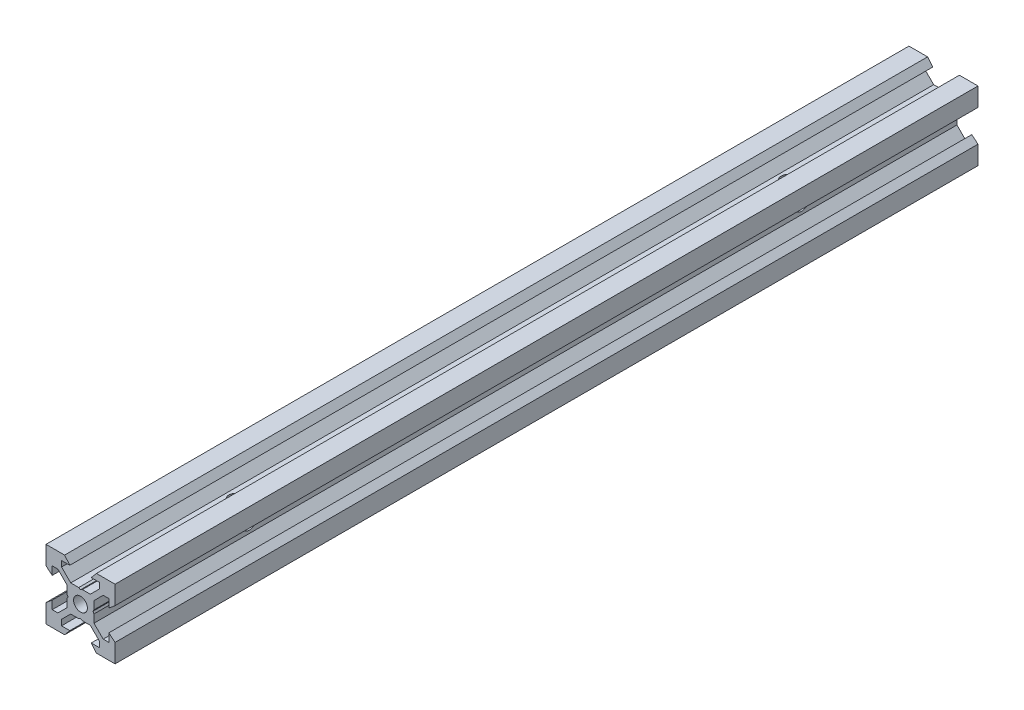
SolidWorks part; units mm, degrees
material "3.3535 (EN-AW 5754)"
ref_plane "Front Plane" through (0, 0, 0) normal (0, 0, 1) x (1, 0, 0)
ref_plane "Top Plane" through (0, 0, 0) normal (0, 1, 0) x (1, 0, 0)
ref_plane "Right Plane" through (0, 0, 0) normal (1, 0, 0) x (0, 0, -1)
sketch "Sketch1" plane through (0, 0, 0) normal (0, 0, 1) x (1, 0, 0)
  line L0 (10, 10) -> (4.6104, 10) construction
  line L1 (10, 10) -> (10, 4.6104) construction
  line L2 (10, -10) -> (10, -4.6104) construction
  line L3 (10, -10) -> (4.6104, -10) construction
  line L4 (10, 10) -> (10, 4.6104)
  line L5 (6.5607, 5.5) -> (8.2, 5.5)
  line L6 (5.5, 8.2) -> (5.5, 6.5607)
  line L7 (10, 10) -> (4.6104, 10)
  line L8 (10, 10) -> (10, 4.6104)
  line L9 (6.5607, 5.5) -> (3.9, 2.8393)
  line L10 (5.5, 6.5607) -> (2.8393, 3.9)
  line L11 (10, 4.6104) -> (8.2, 3.1)
  line L12 (4.6104, 10) -> (3.1, 8.2)
  line L13 (8.2, 3.1) -> (8.2, 5.5)
  line L14 (3.1, 8.2) -> (5.5, 8.2)
  line L15 (-6.5607, 5.5) -> (-8.2, 5.5)
  line L16 (6.5607, -5.5) -> (8.2, -5.5)
  line L17 (3.1, -8.2) -> (5.5, -8.2)
  line L18 (8.2, -3.1) -> (8.2, -5.5)
  line L19 (4.6104, -10) -> (3.1, -8.2)
  line L20 (10, -4.6104) -> (8.2, -3.1)
  line L21 (0.5196, -3.9) -> (0, -3.6)
  line L22 (0.5196, 3.9) -> (0, 3.6)
  line L23 (3.6, 0) -> (3.9, -0.5196)
  line L24 (3.9, 0.5196) -> (3.6, 0)
  line L25 (3.9, 0.5196) -> (3.9, 2.8393)
  line L26 (2.8393, 3.9) -> (0.5196, 3.9)
  line L27 (3.9, -2.8393) -> (3.9, -0.5196)
  line L28 (2.8393, -3.9) -> (0.5196, -3.9)
  line L29 (5.5, -6.5607) -> (2.8393, -3.9)
  line L30 (6.5607, -5.5) -> (3.9, -2.8393)
  line L31 (10, -10) -> (10, -4.6104)
  line L32 (10, -10) -> (4.6104, -10)
  line L33 (5.5, -8.2) -> (5.5, -6.5607)
  line L34 (-6.5607, -5.5) -> (-8.2, -5.5)
  line L35 (10, -10) -> (10, -4.6104)
  line L36 (0, 0) -> (0, 8.2) construction
  line L37 (-10, -10) -> (-4.6104, -10) construction
  line L38 (-10, -10) -> (-10, -4.6104) construction
  line L39 (-10, 10) -> (-10, 4.6104) construction
  line L40 (-10, 10) -> (-4.6104, 10) construction
  line L41 (-10, -10) -> (-10, -4.6104)
  line L43 (-5.5, -8.2) -> (-5.5, -6.5607)
  line L44 (-10, -10) -> (-4.6104, -10)
  line L45 (-10, -10) -> (-10, -4.6104)
  line L46 (-6.5607, -5.5) -> (-3.9, -2.8393)
  line L47 (-5.5, -6.5607) -> (-2.8393, -3.9)
  line L48 (-2.8393, -3.9) -> (-0.5196, -3.9)
  line L49 (-3.9, -2.8393) -> (-3.9, -0.5196)
  line L50 (-2.8393, 3.9) -> (-0.5196, 3.9)
  line L51 (-3.9, 0.5196) -> (-3.9, 2.8393)
  line L52 (-3.9, 0.5196) -> (-3.6, 0)
  line L53 (-3.6, 0) -> (-3.9, -0.5196)
  line L54 (-0.5196, 3.9) -> (0, 3.6)
  line L55 (-0.5196, -3.9) -> (0, -3.6)
  line L56 (-10, -4.6104) -> (-8.2, -3.1)
  line L57 (-4.6104, -10) -> (-3.1, -8.2)
  line L58 (-8.2, -3.1) -> (-8.2, -5.5)
  line L59 (-3.1, -8.2) -> (-5.5, -8.2)
  line L60 (-10, -10) -> (10, -10) construction
  line L61 (-10, -10) -> (-10, 10) construction
  line L62 (-3.1, 8.2) -> (-5.5, 8.2)
  line L63 (-8.2, 3.1) -> (-8.2, 5.5)
  line L64 (-4.6104, 10) -> (-3.1, 8.2)
  line L65 (-10, 4.6104) -> (-8.2, 3.1)
  line L66 (-5.5, 6.5607) -> (-2.8393, 3.9)
  line L67 (-6.5607, 5.5) -> (-3.9, 2.8393)
  line L68 (-10, 10) -> (-10, 4.6104)
  line L69 (-10, 10) -> (-4.6104, 10)
  line L70 (-5.5, 8.2) -> (-5.5, 6.5607)
  line L71 (-10, 10) -> (10, 10) construction
  line L72 (-10, 10) -> (-10, 4.6104)
  line L73 (10, -10) -> (10, 10) construction
  line L74 (-10, -10) -> (10, 10) construction
  line L75 (-10, 10) -> (10, -10) construction
  circle A0 centre (0, 0) radius 2
  dimension "D7" = 4
  dimension "D1" = 20
  dimension "D2" = 5.3896
  dimension "D3" = 4.5
  dimension "D4" = 50
  dimension "D5" = 1.8
  dimension "D6" = 1.5104
  dimension "D8" = 5.5
  dimension "D9" = 120
  dimension "D10" = 0.3
  dimension "D11" = 2.3197
  dimension "D12" = 7.8
  dimension "D13" = 7.8
  dimension "D14" = 1.5
  dimension "D15" = 2.6607
extrude "Boss-Extrude1" add sketch "Sketch1" along normal blind 250 contours L70 L62 L64 L69 L68 L65 L63 L15 L67 L51 L52 L53 L49 L46 L34 L58 L56 L41 L44 L57 L59 L43 L47 L48 L55 L21 L28 L29 L33 L17 L19 L32 L31 L20 L18 L16 L30 L27 L23 L24 L25 L9 L5 L13 L11 L4 L7 L12 L14 L6 L10 region at (9.7172, 7.3052, 0)
sketch "Sketch2" plane through (0, -3.9, 0) normal (0, -1, 0) x (-1, 0, 0)
  line L0 (0, -250) -> (0, -205) construction
  line L1 (0, -250) -> (0, 0) construction
  line L2 (0, 0) -> (0, -45) construction
  circle A0 centre (0, -205) radius 2
  circle A1 centre (0, -45) radius 2
  dimension "D2" = 4
  dimension "D4" = 4
  dimension "D1" = 45
  dimension "D3" = 45
extrude "Cut-Extrude1" cut sketch "Sketch2" against normal through all both and the other way through all
sketch "Sketch3" plane through (3.9, 0, 0) normal (1, 0, 0) x (0, 0, -1)
  line L0 (0, 0) -> (-45, 0) construction
  line L1 (-250, 0) -> (0, 0) construction
  line L2 (-250, 0) -> (-205, 0) construction
  circle A0 centre (-45, 0) radius 2
  circle A1 centre (-205, 0) radius 2
  dimension "D2" = 4
  dimension "D4" = 4
  dimension "D1" = 45
  dimension "D3" = 45
extrude "Cut-Extrude2" cut sketch "Sketch3" against normal through all both
